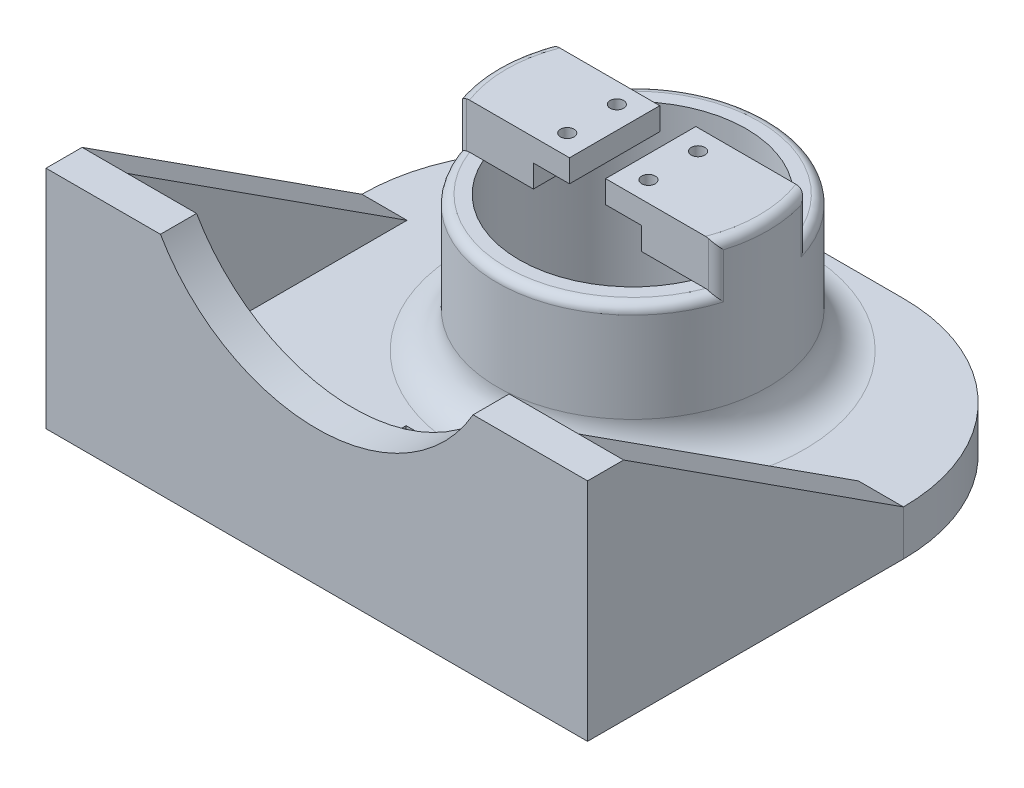
SolidWorks part; units mm, degrees
ref_plane "Front Plane" through (0, 0, 0) normal (0, 0, 1) x (1, 0, 0)
ref_plane "Top Plane" through (0, 0, 0) normal (0, 1, 0) x (1, 0, 0)
ref_plane "Right Plane" through (0, 0, 0) normal (1, 0, 0) x (0, 0, -1)
sketch "Sketch2" plane through (0, 0, 0) normal (0, 1, 0) x (1, 0, 0)
  line L0 (0, 49.9838) -> (0, -58.6525) construction
  line L2 (-60, -70) -> (60, -70)
  line L7 (-60, -70) -> (-60, 40)
  line L8 (-60, 40) -> (60, 40)
  line L9 (60, -70) -> (60, 40)
  line L10 (-60, -70) -> (60, 40) construction
  line L11 (-60, 40) -> (60, -70) construction
  point P3 (0, -15)
  dimension "D1" = 120
  dimension "D2" = 110
  dimension "D3" = 15
extrude "Boss-Extrude1" add sketch "Sketch2" along normal blind 10
sketch "Sketch3" plane through (0, 10, 0) normal (0, 1, 0) x (1, 0, 0)
  line L0 (0, -52.9301) -> (0, 51.772) construction
  circle A1 centre (0, 0) radius 30
  dimension "D1" = 60
extrude "Boss-Extrude2" add sketch "Sketch3" along normal blind 30
sketch "Sketch6" plane through (0, 40, 0) normal (0, 1, 0) x (1, 0, 0)
  circle A0 centre (0, 0) radius 25.15
  dimension "D1" = 50.3
extrude "Cut-Extrude1" cut sketch "Sketch6" against normal through all
sketch "Sketch8" plane through (0, 10, 0) normal (0, 1, 0) x (1, 0, 0)
  line L0 (0, 0) -> (0, -70) construction
  line L1 (-60, -70) -> (60, -70) construction
  line L2 (-23.6557, -50) -> (29.1004, -50) construction
  line L3 (10.3, -31.3978) -> (10.3, -63.6631) construction
  line L9 (-10.7, -60.5) -> (31.3, -60.5)
  line L10 (-10.7, -60.5) -> (-10.7, -39.5)
  line L11 (-10.7, -39.5) -> (31.3, -39.5)
  line L12 (31.3, -60.5) -> (31.3, -39.5)
  line L13 (-10.7, -60.5) -> (31.3, -39.5) construction
  line L14 (-10.7, -39.5) -> (31.3, -60.5) construction
  circle A2 centre (35.2, -45) radius 2.25
  circle A3 centre (35.2, -55) radius 2.25
  circle A4 centre (-14.6, -55) radius 2.25
  circle A5 centre (-14.6, -45) radius 2.25
  point P7 (10.3, -50)
  dimension "D4" = 4.5
  dimension "D1" = 50
  dimension "D2" = 42
  dimension "D3" = 21
  dimension "D5" = 10
  dimension "D6" = 10.3
  dimension "D7" = 49.8
extrude "Cut-Extrude2" cut sketch "Sketch8" against normal through all
sketch "Sketch9" plane through (0, 40, 0) normal (0, 1, 0) x (1, 0, 0)
  line L0 (0, 30) -> (0, -30) construction
  line L1 (-30, 0) -> (30, 0) construction
  line L2 (-28.2843, -10) -> (-4, -10)
  line L3 (-4, -10) -> (-4, 10)
  line L4 (-28.2843, 10) -> (-4, 10)
  line L5 (28.2843, -10) -> (4, -10)
  line L6 (4, -10) -> (4, 10)
  line L7 (28.2843, 10) -> (4, 10)
  circle A0 centre (0, 0) radius 30 construction
  circle A1 centre (0, 0) radius 30 construction
  arc A2 (-28.2843, 10) -> (-28.2843, -10) centre (0, 0) ccw
  circle A3 centre (-9, -5.5) radius 1.5
  circle A4 centre (-9, 5.5) radius 1.5
  circle A5 centre (9, -5.5) radius 1.5
  circle A6 centre (9, 5.5) radius 1.5
  arc A7 (28.2843, -10) -> (28.2843, 10) centre (0, 0) ccw
  point P14 (-4, 0)
  dimension "D5" = 3
  dimension "D1" = 20
  dimension "D2" = 11
  dimension "D3" = 9
  dimension "D4" = 8
extrude "Boss-Extrude3" add sketch "Sketch9" along normal blind 10
sketch "Sketch10" plane through (0, 0, 0) normal (0, 0, 1) x (1, 0, 0)
  line L0 (0, 40) -> (0, 60.9834) construction
  line L1 (28.2843, 40) -> (-28.2843, 40) construction
  line L2 (-12, 40) -> (-12, 45)
  line L3 (-12, 45) -> (12, 45)
  line L5 (12, 40) -> (-12, 40)
  line L6 (12, 40) -> (12, 45)
  point P10 (0, 45)
  dimension "D1" = 24
  dimension "D2" = 5
extrude "Cut-Extrude3" cut sketch "Sketch10" against normal mid plane 20
fillet "Fillet1" radius 8 1 edges at (0, 10, 30)
fillet "Fillet2" radius 2 8 edges at (-30, 50, 0) (28.2843, 45, 10) (30, 50, 0) (28.2843, 45, -10) (0, 40, -30) (-28.2843, 45, -10) (-28.2843, 45, 10) (0, 40, 30)
sketch "Sketch11" plane through (0, 10, 0) normal (0, 1, 0) x (1, 0, 0)
  line L0 (60, -70) -> (60, 40) construction
  line L1 (-60, -70) -> (60, -70)
  line L2 (-60, -70) -> (-60, -62)
  line L3 (-60, -62) -> (60, -62)
  line L4 (60, -70) -> (60, -62)
  dimension "D1" = 8
extrude "Boss-Extrude4" add sketch "Sketch11" along normal blind 40
sketch "Sketch12" plane through (60, 0, 0) normal (1, 0, 0) x (0, 0, -1)
  line L0 (-62, 50) -> (0, 10)
  line L1 (-62, 10) -> (40, 10) construction
  line L2 (0, 10) -> (-62, 10)
  line L3 (-62, 10) -> (-62, 50)
extrude "Boss-Extrude5" add sketch "Sketch12" against normal blind 10
mirror "Mirror1" about plane through (0, 0, 0) normal (1, 0, 0) of "Boss-Extrude5"
ref_axis "Axis1" through (0, 0, 0) along (0, 1, 0)
fillet "Fillet3" radius 40 2 edges at (60, 5, -40) (-60, 5, -40)
sketch "Sketch14" plane through (0, 0, 62) normal (0, 0, -1) x (-1, 0, 0)
  line L0 (0, 50) -> (0, 154.9898) construction
  line L1 (60, 50) -> (-60, 50) construction
  circle A0 centre (0, 70) radius 40
  dimension "D1" = 80
  dimension "D2" = 20
extrude "Cut-Extrude4" cut sketch "Sketch14" against normal through all
